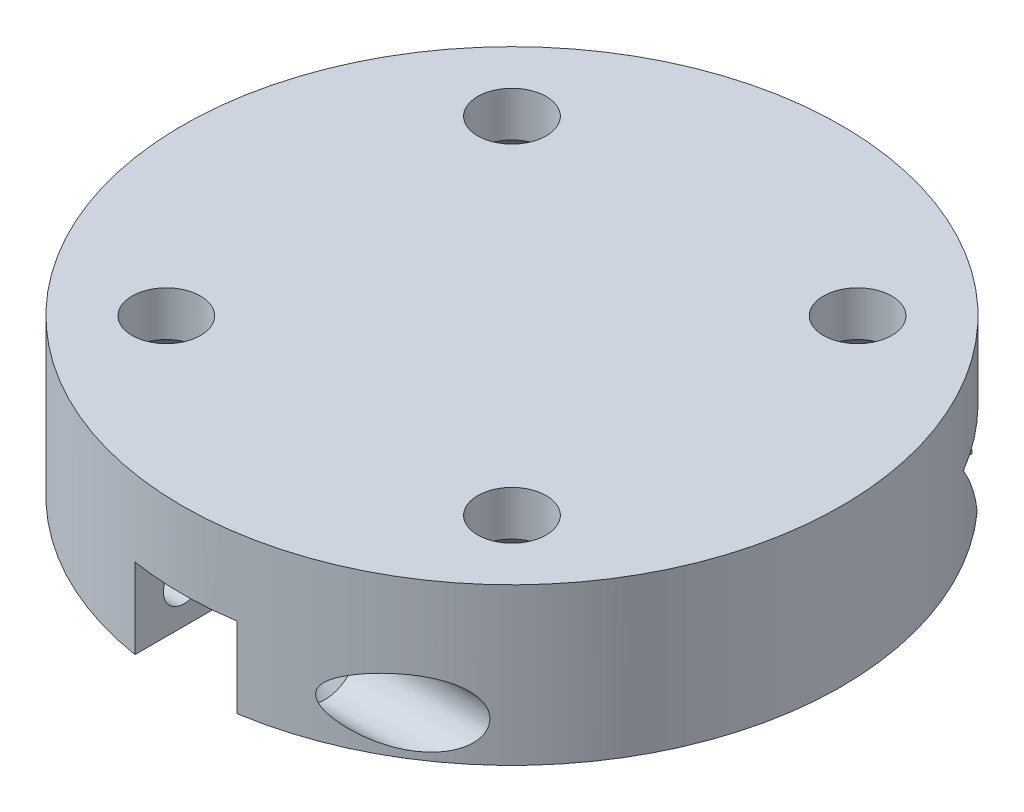
SolidWorks part; units mm, degrees
material "ABS"
ref_plane "Front Plane" through (0, 0, 0) normal (0, 0, 1) x (1, 0, 0)
ref_plane "Top Plane" through (0, 0, 0) normal (0, 1, 0) x (1, 0, 0)
ref_plane "Right Plane" through (0, 0, 0) normal (1, 0, 0) x (0, 0, -1)
sketch "Sketch63" plane through (0, 0, 0) normal (0, 1, 0) x (1, 0, 0)
  circle A0 centre (0, 0) radius 33.71
  dimension "D1" = 67.42
extrude "Boss-Extrude14" add sketch "Sketch63" along normal blind 30
sketch "Sketch67" plane through (0, 0, 0) normal (0, 0, 1) x (1, 0, 0)
  line L0 (33.6358, 0) -> (-33.71, 0)
  line L10 (-33.71, 0) -> (33.71, 0) construction
  line L11 (-33.71, 0) -> (33.71, 0)
  line L12 (-5.2183, -0.0845) -> (-9.0815, 8.2)
  line L13 (-9.0815, 8.2) -> (9.0073, 8.2)
  line L14 (9.0073, 8.2) -> (5.1442, -0.0845)
  line L15 (19.7817, -0.0845) -> (15.9185, 8.2)
  line L16 (15.9185, 8.2) -> (29.0073, 8.2)
  line L17 (29.0073, 8.2) -> (25.1442, -0.0845)
  line L18 (-25.2183, -0.0845) -> (-29.0815, 8.2)
  line L19 (-29.0815, 8.2) -> (-15.9927, 8.2)
  line L20 (-15.9927, 8.2) -> (-19.8558, -0.0845)
extrude "Cut-Extrude16" cut sketch "Sketch67" against normal through all from offset 1.56 contours L20 L19 L18 L0 | L17 L16 L15 L11 region at (-22.5371, 4.664, 0) region at (22.4629, 4.664, 0) offset against normal yes
extrude "Cut-Extrude17" cut sketch "Sketch67<3>" against normal through all both and the other way through all contours L14 L13 L12 L11 region at (-0.0371, 4.4663, 0)
sketch "Sketch67<3>" plane through (0, 0, 0) normal (0, 0, 1) x (1, 0, 0) same geometry as "Sketch67"
sketch "Sketch68" plane through (0, 0, 0) normal (0, -1, 0) x (1, 0, 0)
  line L0 (5.1836, 33.3091) -> (5.1836, 21.2974)
  line L1 (5.1836, -33.3091) -> (5.1836, 33.3091) construction
  line L2 (5.1836, 21.2974) -> (15.0554, 21.2974)
  line L3 (15.0554, 21.2974) -> (15.0554, 48.9247)
  line L4 (15.0554, 48.9247) -> (-18.415, 48.9247)
  line L5 (-18.415, 48.9247) -> (-18.415, 21.2974)
  line L6 (-18.415, 21.2974) -> (-5.2578, 21.2974)
  line L7 (-5.2578, 33.2974) -> (-5.2578, -33.2974) construction
  line L8 (-5.2578, 21.2974) -> (-5.2578, 33.2974)
  circle A1 centre (0, 0) radius 33.71
  line M9 (-5.2578, -33.2974) -> (-5.2578, 33.2974)
  arc M10 (-5.2578, 33.2974) -> (-25.2578, -22.3251) centre (0, 0) ccw
  dimension "D1" = 12
extrude "Boss-Extrude15" add sketch "Sketch68" against normal blind 12 contours L5 L6 M9 M10 | L3 A1 L0 L2 region at (9.8792, 0, 26.6954) region at (-11.2872, 0, 26.4061)
ref_plane "Plane8" through (-0.0378, 0, 0) normal (1, 0, 0) x (0, 0, -1)
sketch "Sketch69" plane through (-0.0378, 0, 0) normal (1, 0, 0) x (0, 0, -1)
  line L0 (-33.2974, 0) -> (-21.2974, 0) construction
  line L1 (-33.2974, 8.2) -> (-33.2974, 0) construction
  circle A0 centre (-28.2974, 4.1) radius 2.1
  dimension "D1" = 4.2
  dimension "D2" = 4.1
  dimension "D3" = 5
extrude "Cut-Extrude18" cut sketch "Sketch69" against normal blind 6 from surface starting at face at (-5.2578, 4.1, 27.2974)
ref_plane "Plane9" through (9.1836, 0, 0) normal (-1, 0, 0) x (0, 0, 1)
sketch "Sketch70" plane through (9.1836, 0, 0) normal (-1, 0, 0) x (0, 0, 1)
  circle A0 centre (28.2974, 4.1) radius 2.1 construction
  circle A1 centre (28.2974, 4.1) radius 2.1
  circle A2 centre (28.2974, 4.1) radius 3.36
  dimension "D1" = 6.72
extrude "Cut-Extrude19" cut sketch "Sketch70" against normal through all contours A1 | A2 A1 region at (9.1836, 4.1, 28.2974) region at (9.1836, 4.1, 25.0325)
hole_wizard "CSK for M3 Hex Socket Countersunk Cap Screw9" positions "Sketch71" profile "Sketch73" countersink size "M3" standard "ISO"
sketch "Sketch71" plane through (9.1836, 0, 0) normal (1, 0, 0) x (0, 0, -1)
  point P0 (-28.2974, 4.1)
sketch "Sketch73" plane through (9.1836, 4.1, 28.2974) normal (0, 1, 0) x (0, 0, -1)
  line L0 (0, 0) -> (0, 15.5219)
  line L1 (0, 15.5219) -> (1.8, 14.4404)
  line L2 (1.8, 14.4404) -> (1.8, 1.56)
  line L3 (1.8, 1.56) -> (3.36, 0)
  line L5 (3.36, 0) -> (0, 0)
  line L6 (-1.8, 1.56) -> (-3.36, 0) construction
  line L10 (0, 15.5219) -> (-1.8, 14.4404) construction
  line L11 (0, -6.35) -> (0, 107.95) construction
  dimension "Hole Dia." = 3.6
  dimension "Hole Depth" = 14.4404
  dimension "Near C'Sink Dia." = 6.72
  dimension "Near C'Sink Angle" = 90
  dimension "Drill Angle" = 118
sketch "Sketch74" plane through (0, 30, 0) normal (0, 1, 0) x (1, 0, 0)
  circle A0 centre (0, 0) radius 44.6148
extrude "Cut-Extrude20" cut sketch "Sketch74" against normal blind 14
sketch "Sketch75" plane through (0, 16, 0) normal (0, 1, 0) x (1, 0, 0)
  circle A0 centre (0, 0) radius 31.75
  circle A1 centre (0, 0) radius 33.71
extrude "Boss-Extrude16" [suppressed] add sketch "Sketch75" along normal blind 3
sketch "Sketch76" plane through (0, 8.2, 0) normal (0, -1, 0) x (1, 0, 0)
  line L0 (-17.6777, 17.6777) -> (17.6777, -17.6777)
  line L1 (17.6777, 17.6777) -> (-17.6777, -17.6777)
  line L2 (0, 0) -> (0, 47.0696)
  circle A0 centre (0, 0) radius 25
  dimension "D1" = 50
  dimension "D2" = 90
  dimension "D3" = 45
hole_wizard "CSK for M6 Hex Socket Countersunk Cap Screw4" positions "Sketch77" profile "Sketch78" countersink size "M6" standard "ISO"
sketch "Sketch77" plane through (0, 8.2, 0) normal (0, -1, 0) x (-1, 0, 0)
  point P0 (17.6777, -17.6777)
  point P3 (-17.6777, -17.6777)
  point P6 (17.6777, 17.6777)
  point P9 (-17.6777, 17.6777)
sketch "Sketch78" plane through (-17.6777, 8.2, 17.6777) normal (1, 0, 0) x (0, 0, -1)
  line L0 (0, 0) -> (0, 16.543)
  line L1 (0, 16.543) -> (3.5, 14.44)
  line L2 (3.5, 14.44) -> (3.5, 3.22)
  line L3 (3.5, 3.22) -> (6.72, 0)
  line L5 (6.72, 0) -> (0, 0)
  line L6 (-3.5, 3.22) -> (-6.72, 0) construction
  line L10 (0, 16.543) -> (-3.5, 14.44) construction
  line L11 (0, -6.35) -> (0, 107.95) construction
  dimension "Hole Dia." = 7
  dimension "Hole Depth" = 14.44
  dimension "Near C'Sink Dia." = 13.44
  dimension "Near C'Sink Angle" = 90
  dimension "Drill Angle" = 118
sketch "Sketch79" plane through (0, 8.2, 0) normal (0, -1, 0) x (1, 0, 0)
  circle A0 centre (-17.6777, -17.6777) radius 6.72
  circle A1 centre (17.6777, -17.6777) radius 6.72
  circle A2 centre (17.6777, 17.6777) radius 6.72
  circle A3 centre (-17.6777, 17.6777) radius 6.72
extrude "Cut-Extrude21" cut sketch "Sketch79" along normal blind 15
